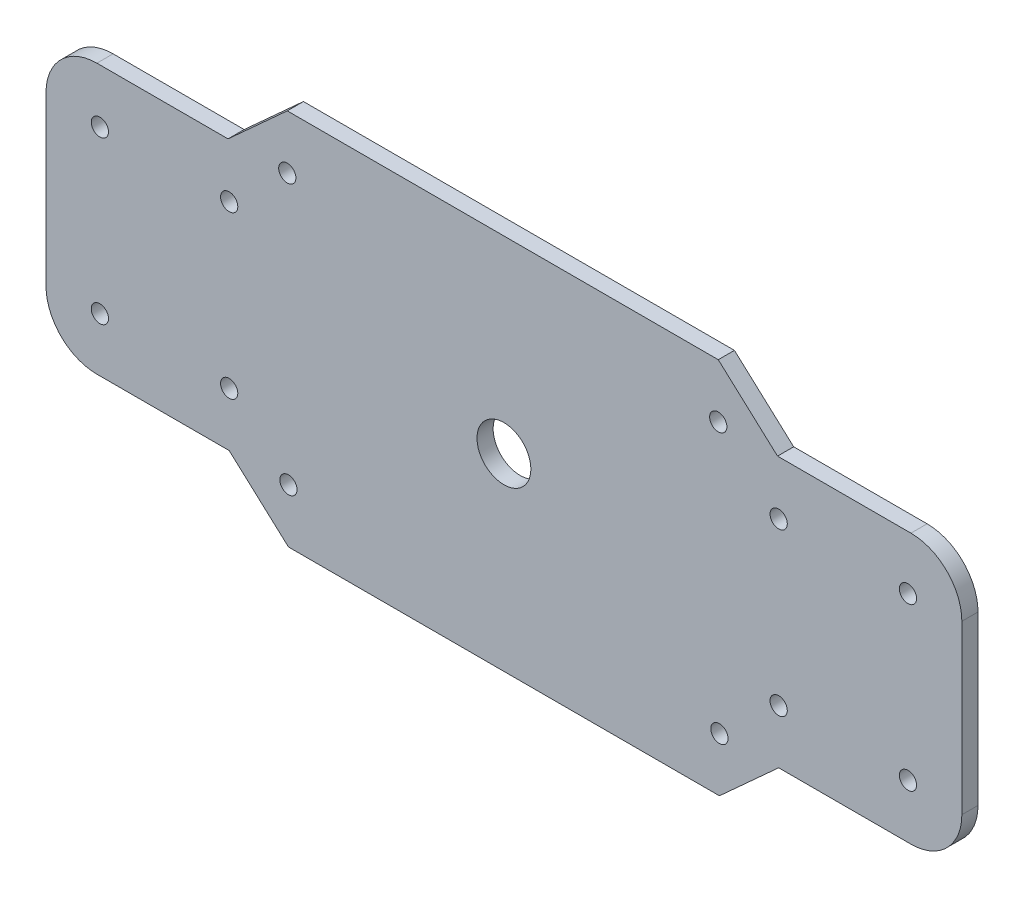
SolidWorks part; units mm, degrees
ref_plane "Front Plane" through (0, 0, 0) normal (0, 0, 1) x (1, 0, 0)
ref_plane "Top Plane" through (0, 0, 0) normal (0, 1, 0) x (1, 0, 0)
ref_plane "Right Plane" through (0, 0, 0) normal (1, 0, 0) x (0, 0, -1)
sketch "Sketch2" plane through (0, 0, 0) normal (0, 0, 1) x (1, 0, 0)
  line L0 (-47.8745, 29.703) -> (-36.8745, 39.703)
  line L5 (-72.2113, 29.703) -> (-47.8745, 29.703)
  line L6 (-81.6615, 20.2529) -> (-81.6615, -10.8468)
  line L7 (-72.2113, -20.297) -> (-47.6615, -20.297)
  line L8 (88.3385, 20.2529) -> (88.3385, -10.8468)
  line L9 (-36.8745, 39.703) -> (43.1255, 39.703)
  line L10 (43.1255, 39.703) -> (54.1255, 29.703)
  line L11 (-47.6615, -20.297) -> (-36.6615, -30.297)
  line L12 (-36.6615, -30.297) -> (43.3385, -30.297)
  line L13 (43.3385, -30.297) -> (54.3385, -20.297)
  line L14 (54.1255, 29.703) -> (78.8883, 29.703)
  line L15 (54.3385, -20.297) -> (78.8883, -20.297)
  arc A0 (-72.2113, 29.703) -> (-81.6615, 20.2529) centre (-72.2113, 20.2529) ccw
  arc A1 (-81.6615, -10.8468) -> (-72.2113, -20.297) centre (-72.2113, -10.8468) ccw
  arc A2 (88.3385, 20.2529) -> (78.8883, 29.703) centre (78.8883, 20.2529) ccw
  arc A3 (78.8883, -20.297) -> (88.3385, -10.8468) centre (78.8883, -10.8468) ccw
  circle A4 centre (-47.6615, 19.703) radius 1.6
  circle A5 centre (-71.6615, 19.703) radius 1.6
  circle A6 centre (-71.6615, -10.297) radius 1.6
  circle A7 centre (-47.6615, -10.297) radius 1.6
  circle A8 centre (78.3385, -10.297) radius 1.6
  circle A9 centre (54.3385, -10.297) radius 1.6
  circle A10 centre (78.3385, 19.703) radius 1.6
  circle A11 centre (54.3385, 19.703) radius 1.6
  circle A12 centre (3.3385, 4.703) radius 5
  circle A13 centre (-36.8745, 29.703) radius 1.6
  circle A14 centre (-36.6615, -20.297) radius 1.6
  circle A15 centre (43.3385, -20.297) radius 1.6
  circle A16 centre (43.1255, 29.703) radius 1.6
extrude "Boss-Extrude4" add sketch "Sketch2" along normal blind 3
